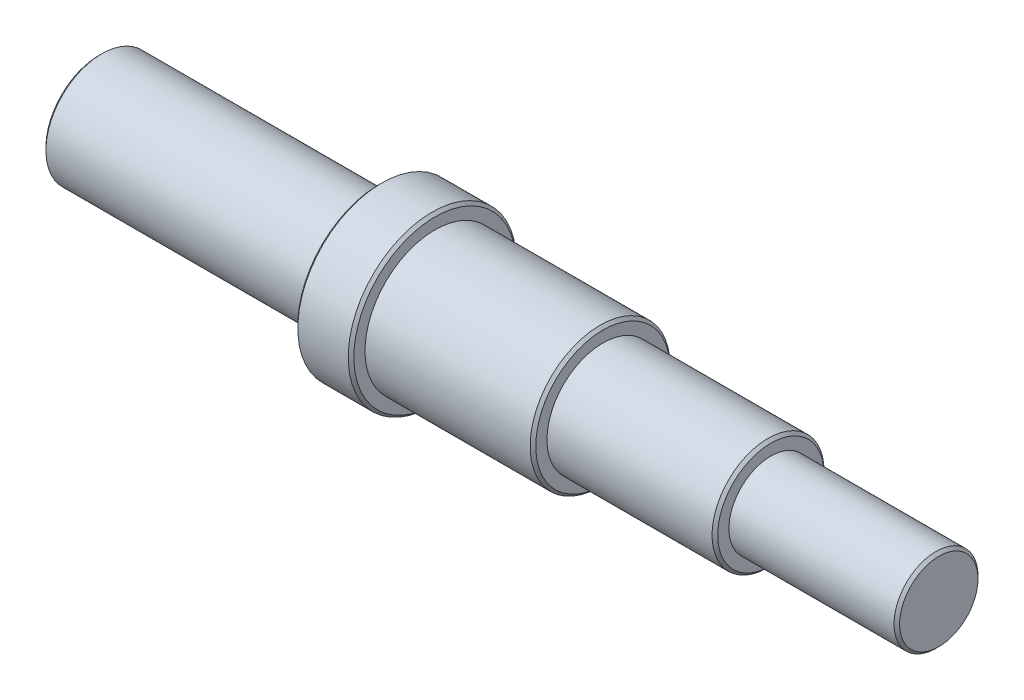
SolidWorks part; units mm, degrees
ref_plane "前视基准面" through (0, 0, 0) normal (0, 0, 1) x (1, 0, 0)
ref_plane "上视基准面" through (0, 0, 0) normal (0, 1, 0) x (1, 0, 0)
ref_plane "右视基准面" through (0, 0, 0) normal (1, 0, 0) x (0, 0, -1)
ref_axis "基准轴1" through (88.99, 0, 0) along (-1, 0, 0)
sketch "草图1" plane through (0, 0, 0) normal (1, 0, 0) x (0, 0, -1)
  circle A0 centre (0, 0) radius 10
extrude "凸台-拉伸1" add sketch "草图1" along normal blind 50
chamfer "倒角1" distance 0.5 angle 45 1 edges at (0, 0, -10)
sketch "草图2" plane through (50, 0, 0) normal (1, 0, 0) x (0, 0, -1)
  circle A0 centre (0, 0) radius 15
extrude "凸台-拉伸2" add sketch "草图2" along normal blind 10
chamfer "倒角2" distance 0.5 angle 45 1 edges at (50, 0, -15)
chamfer "倒角3" distance 0.5 angle 45 1 edges at (60, 0, -15)
sketch "草图3" plane through (60, 0, 0) normal (1, 0, 0) x (0, 0, -1)
  circle A0 centre (0, 0) radius 12.5
extrude "凸台-拉伸3" add sketch "草图3" along normal blind 30
chamfer "倒角4" distance 0.5 angle 45 1 edges at (90, 0, -12.5)
sketch "草图4" plane through (90, 0, 0) normal (1, 0, 0) x (0, 0, -1)
  circle A0 centre (0, 0) radius 10
extrude "凸台-拉伸4" add sketch "草图4" along normal blind 30
chamfer "倒角5" distance 0.5 angle 45 1 edges at (120, 0, -10)
sketch "草图5" plane through (120, 0, 0) normal (1, 0, 0) x (0, 0, -1)
  circle A0 centre (0, 0) radius 7.5
extrude "凸台-拉伸5" add sketch "草图5" along normal blind 30
chamfer "倒角6" distance 0.5 angle 45 1 edges at (150, 0, -7.5)
